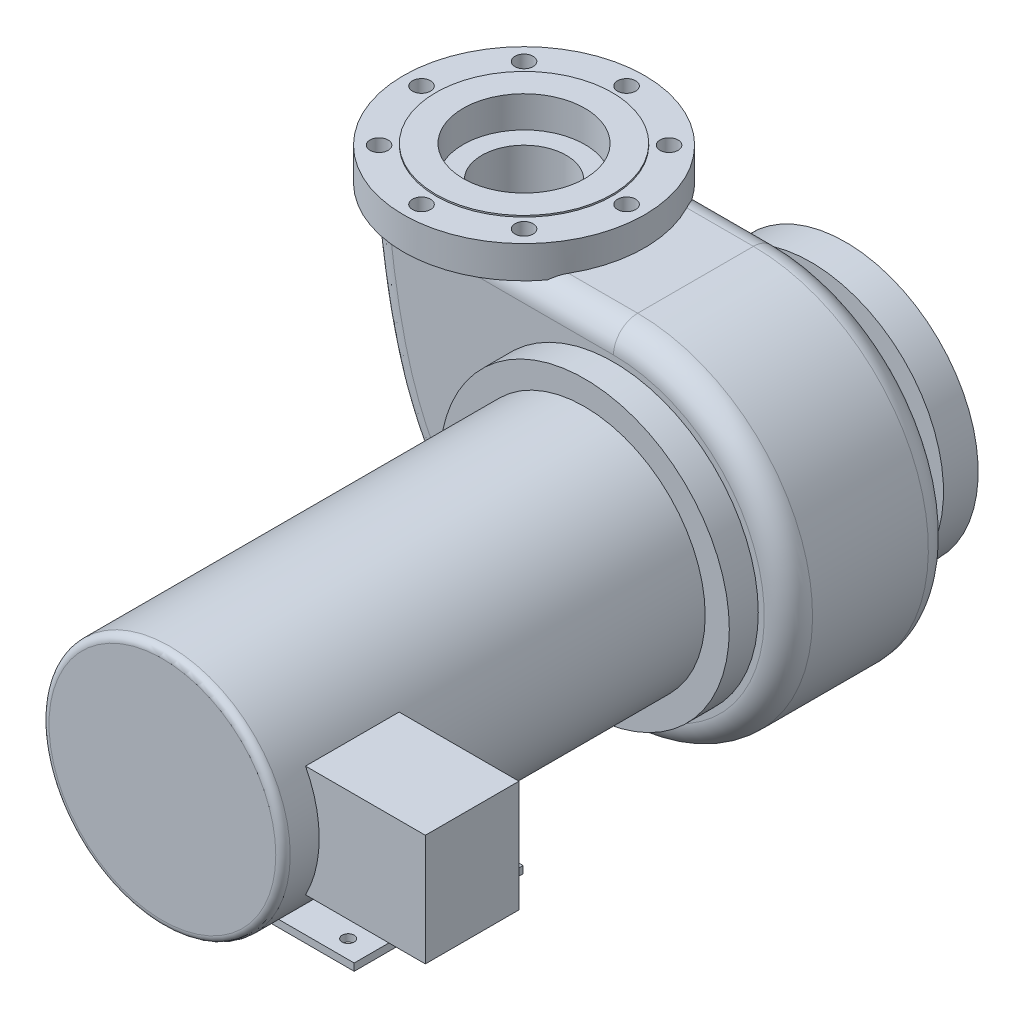
SolidWorks part; units mm, degrees
material "Cast Carbon Steel"
ref_plane "Front Plane" through (0, 0, 0) normal (0, 0, 1) x (1, 0, 0)
ref_plane "Top Plane" through (0, 0, 0) normal (0, 1, 0) x (1, 0, 0)
ref_plane "Right Plane" through (0, 0, 0) normal (1, 0, 0) x (0, 0, -1)
other "Configuration Table"
sketch "Sketch1" plane through (0, 0, 0) normal (0, 0, 1) x (1, 0, 0)
  circle A0 centre (0, 0) radius 127
  dimension "D1" = 254
extrude "Boss-Extrude1" add sketch "Sketch1" against normal blind 444.5
ref_plane "Motor_base_plane" through (0, -133.35, 0) normal (0, 1, 0) x (-1, 0, 0)
ref_axis "Axis1" through (0, 0, -459.5772) along (0, 0, 1)
sketch "Sketch2" plane through (0, -133.35, 0) normal (0, 1, 0) x (-1, 0, 0)
  line L0 (127, 0) -> (-127, 0) construction
  line L1 (133.35, -68.58) -> (-133.35, -68.58)
  line L2 (133.35, -68.58) -> (133.35, -246.38)
  line L3 (133.35, -246.38) -> (-133.35, -246.38)
  line L4 (-133.35, -68.58) -> (-133.35, -246.38)
  line L5 (133.35, -68.58) -> (-133.35, -246.38) construction
  line L6 (133.35, -246.38) -> (-133.35, -68.58) construction
  line L7 (0, 0) -> (0, -500.7637) construction
  line L8 (-107.95, -227.33) -> (107.95, -227.33) construction
  circle A0 centre (-107.95, -227.33) radius 6.3326
  circle A1 centre (107.95, -227.33) radius 6.3326
  circle A2 centre (-107.95, -87.63) radius 6.3326
  circle A3 centre (107.95, -87.63) radius 6.3326
  point P0 (0, -157.48)
  dimension "D6" = 12.6652
  dimension "D1" = 68.58
  dimension "D2" = 266.7
  dimension "D3" = 177.8
  dimension "D4" = 107.95
  dimension "D5" = 69.85
  dimension "D9" = 215.9
  dimension "D7" = 2
  dimension "D8" = 2
extrude "Boss-Extrude2" add sketch "Sketch2" along normal blind 7.62 separate body
fillet "Fillet1" radius 7.62 1 edges at (127, 0, 0)
sketch "Sketch3" plane through (0, 0, -444.5) normal (0, 0, -1) x (-1, 0, 0)
  circle A0 centre (0, 0) radius 152.4
  dimension "D1" = 304.8
extrude "Motor-pump-plate" add sketch "Sketch3" along normal blind 30.48
sketch "Sketch5" plane through (0, 0, -474.98) normal (0, 0, -1) x (-1, 0, 0)
  line L0 (182.88, 219.2904) -> (182.88, 0) construction
  line L1 (0, 184.15) -> (264.16, 184.15)
  line L2 (0, 0) -> (0, -236.1444) construction
  line L3 (0, 0) -> (130.2137, -130.2137) construction
  arc A0 (130.2137, -130.2137) -> (0, 184.15) centre (0, 0) cw
  spline S0 degree 3 poles (264.16, 184.15) (256.1218, 110.7163) (240.9801, -17.3305) (160.1258, -100.3016) (130.2137, -130.2137) knots 0 0 0 0 0.655373 1 1 1 1
  dimension "D2" = 182.88
  dimension "D3" = 264.16
  dimension "D4" = 45
extrude "Boss-Extrude4" add sketch "Sketch5" along normal blind 172.72
sketch "Sketch6" plane through (0, 0, -647.7) normal (0, 0, -1) x (-1, 0, 0)
  circle A0 centre (0, 0) radius 87.3125
  dimension "D1" = 174.625
extrude "Boss-Extrude5" add sketch "Sketch6" along normal blind 35.0012
fillet "Fillet2" radius 25.4 3 edges at (-132.08, 184.15, -647.7) (170.1324, -70.4712, -647.7)
fillet "Fillet3" radius 25.4 3 edges at (-132.08, 184.15, -474.98) (170.1324, -70.4712, -474.98)
sketch "Sketch7" plane through (0, 0, -682.7012) normal (0, 0, -1) x (-1, 0, 0)
  circle A0 centre (0, 0) radius 139.7
  dimension "D1" = 279.4
extrude "Boss-Extrude6" add sketch "Sketch7" along normal blind 36.5125
sketch "Sketch8" plane through (0, 0, -719.2137) normal (0, 0, -1) x (-1, 0, 0)
  circle A0 centre (0, 0) radius 92.8688
  dimension "D1" = 185.7375
extrude "Boss-Extrude7" add sketch "Sketch8" along normal blind 1.5875
sketch "Sketch9" plane through (0, 0, -720.8012) normal (0, 0, -1) x (-1, 0, 0)
  circle A0 centre (0, 0) radius 64.0969
  dimension "D1" = 128.1938
extrude "Cut-Extrude1" cut sketch "Sketch9" against normal blind 38.1
sketch "Sketch19" plane through (0, 0, -682.7012) normal (0, 0, -1) x (-1, 0, 0)
  circle A0 centre (0, 0) radius 54.9111
extrude "Cut-Extrude6" cut sketch "Sketch19" against normal blind 101.6
sketch "Sketch10" plane through (0, 0, -719.2137) normal (0, 0, -1) x (-1, 0, 0)
  circle A0 centre (0, 107.95) radius 9.525
  circle A1 centre (76.3322, 76.3322) radius 9.525
  circle A2 centre (107.95, 0) radius 9.525
  circle A3 centre (76.3322, -76.3322) radius 9.525
  circle A4 centre (0, -107.95) radius 9.525
  circle A5 centre (-76.3322, -76.3322) radius 9.525
  circle A6 centre (-107.95, 0) radius 9.525
  circle A7 centre (-76.3322, 76.3322) radius 9.525
  dimension "D1" = 19.05
  dimension "D2" = 107.95
  dimension "D3" = 8
extrude "Cut-Extrude2" cut sketch "Sketch10" against normal up to surface (36.5125 mm away) up to face at (-139.7, 0, -682.7012)
sketch "Sketch11" plane through (0, 184.15, 0) normal (0, 1, 0) x (1, 0, 0)
  line L0 (0, 459.5772) -> (0, 15.0772) construction
  circle A0 centre (-182.88, 563.6467) radius 72.6064
  dimension "D2" = 145.2127
  dimension "D1" = 182.88
extrude "Boss-Extrude8" add sketch "Sketch11" along normal blind 30.1625
sketch "Sketch12" plane through (0, 214.3125, 0) normal (0, 1, 0) x (1, 0, 0)
  circle A0 centre (-182.88, 563.6467) radius 127
  arc A1 (-225.6757, 622.3) -> (-218.5032, 500.38) centre (-182.88, 563.6467) ccw construction
  dimension "D1" = 254
extrude "Boss-Extrude9" add sketch "Sketch12" against normal blind 33.9725
sketch "Sketch13" plane through (0, 214.3125, 0) normal (0, 1, 0) x (1, 0, 0)
  circle A0 centre (-182.88, 563.6467) radius 92.8688
  circle A1 centre (-182.88, 563.6467) radius 127 construction
  dimension "D1" = 185.7375
extrude "Boss-Extrude10" add sketch "Sketch13" along normal blind 1.5875
sketch "Sketch14" plane through (0, 215.9, 0) normal (0, 1, 0) x (1, 0, 0)
  circle A0 centre (-182.88, 563.6467) radius 64.0969
  circle A1 centre (-182.88, 563.6467) radius 92.8688 construction
  dimension "D1" = 128.1938
extrude "Cut-Extrude3" cut sketch "Sketch14" against normal blind 33.02
sketch "Sketch15" plane through (0, 182.88, 0) normal (0, 1, 0) x (1, 0, 0)
  circle A0 centre (-182.88, 563.6467) radius 44.45
  circle A1 centre (-182.88, 563.6467) radius 64.0969 construction
  dimension "D1" = 88.9
extrude "Cut-Extrude4" cut sketch "Sketch15" against normal blind 100.838
sketch "Sketch16" plane through (0, 214.3125, 0) normal (0, 1, 0) x (1, 0, 0)
  circle A0 centre (-182.88, 671.5967) radius 9.525
  circle A1 centre (-182.88, 563.6467) radius 44.45 construction
  circle A2 centre (-106.5478, 639.9788) radius 9.525
  circle A3 centre (-74.93, 563.6467) radius 9.525
  circle A4 centre (-106.5478, 487.3145) radius 9.525
  circle A5 centre (-182.88, 455.6967) radius 9.525
  circle A6 centre (-259.2122, 487.3145) radius 9.525
  circle A7 centre (-290.83, 563.6467) radius 9.525
  circle A8 centre (-259.2122, 639.9788) radius 9.525
  point P4 (-182.88, 563.6467)
  dimension "D1" = 19.05
  dimension "D2" = 107.95
  dimension "D3" = 8
extrude "Cut-Extrude5" cut sketch "Sketch16" against normal up to surface (33.9725 mm away) up to face at (-239.8194, 180.34, -562.6886)
sketch "Sketch18" plane through (0, 0, 0) normal (1, 0, 0) x (0, 0, -1)
  line L0 (459.5772, 0) -> (15.0772, 0) construction
  line L1 (0, 119.38) -> (0, -119.38) construction
  line L2 (38.1, 58.674) -> (136.652, 58.674)
  line L3 (38.1, 58.674) -> (38.1, -58.674)
  line L4 (38.1, -58.674) -> (136.652, -58.674)
  line L5 (136.652, 58.674) -> (136.652, -58.674)
  line L6 (38.1, 58.674) -> (136.652, -58.674) construction
  line L7 (38.1, -58.674) -> (136.652, 58.674) construction
  point P2 (87.376, 0)
  dimension "D1" = 38.1
  dimension "D2" = 98.552
  dimension "D3" = 117.348
extrude "Boss-Extrude11" add sketch "Sketch18" along normal blind 238.76
other "CPoint1" parameters "Diameter"=127, "StubLength"=0
ref_axis "Axis2" through (-182.88, 192.88, -563.6467) along (0, -1, 0)
other "CPoint2" parameters "Diameter"=127, "StubLength"=0
ref_axis "Axis3" through (0, 0, -692.7012) along (0, 0, 1)
